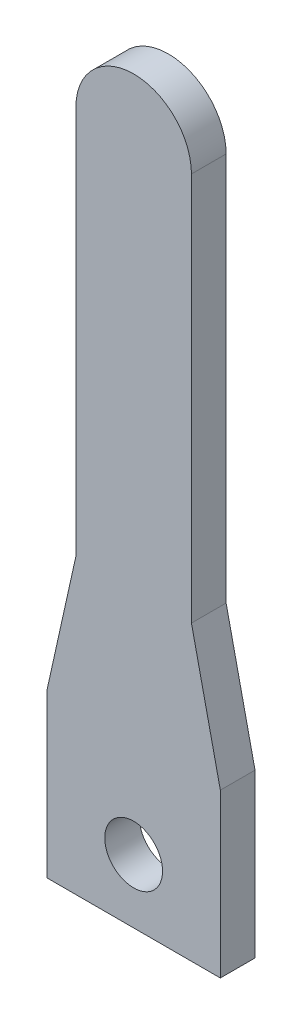
SolidWorks part; units mm, degrees
material "ABS PC"
ref_plane "Front Plane" through (0, 0, 0) normal (0, 0, 1) x (1, 0, 0)
ref_plane "Top Plane" through (0, 0, 0) normal (0, 1, 0) x (1, 0, 0)
ref_plane "Right Plane" through (0, 0, 0) normal (1, 0, 0) x (0, 0, -1)
sketch "Sketch1" plane through (0, 0, 0) normal (0, 0, 1) x (1, 0, 0)
  line L0 (-7.5, -32) -> (7.5, -32)
  line L1 (5, 27) -> (5, -6.6554)
  line L2 (-5, 27) -> (-5, -6.6554)
  line L3 (-7.5, -17.9221) -> (-7.5, -32)
  line L5 (7.5, -17.9221) -> (7.5, -32)
  line L6 (-5, -32) -> (5, -32) construction
  line L7 (-7.5, -34.5) -> (7.5, -34.5) construction
  line L8 (-7.5, -17.9221) -> (-5, -6.6554)
  line L9 (-7.5, 27) -> (-7.5, -34.5) construction
  line L10 (7.5, 27) -> (7.5, -34.5) construction
  line L11 (0, -32) -> (0, 27) construction
  line L12 (7.5, -17.9221) -> (5, -6.6554)
  line L14 (5, 27) -> (5, -32) construction
  line L15 (-5, 27) -> (-5, -32) construction
  arc A0 (5, 27) -> (-5, 27) centre (0, 27) ccw
  circle A1 centre (0, -26.5) radius 2.5
  arc A3 (7.5, 27) -> (-7.5, 27) centre (0, 27) ccw construction
  dimension "D1" = 2.5
  dimension "D3" = 5.5
extrude "Boss-Extrude1" add sketch "Sketch1" along normal blind 3
